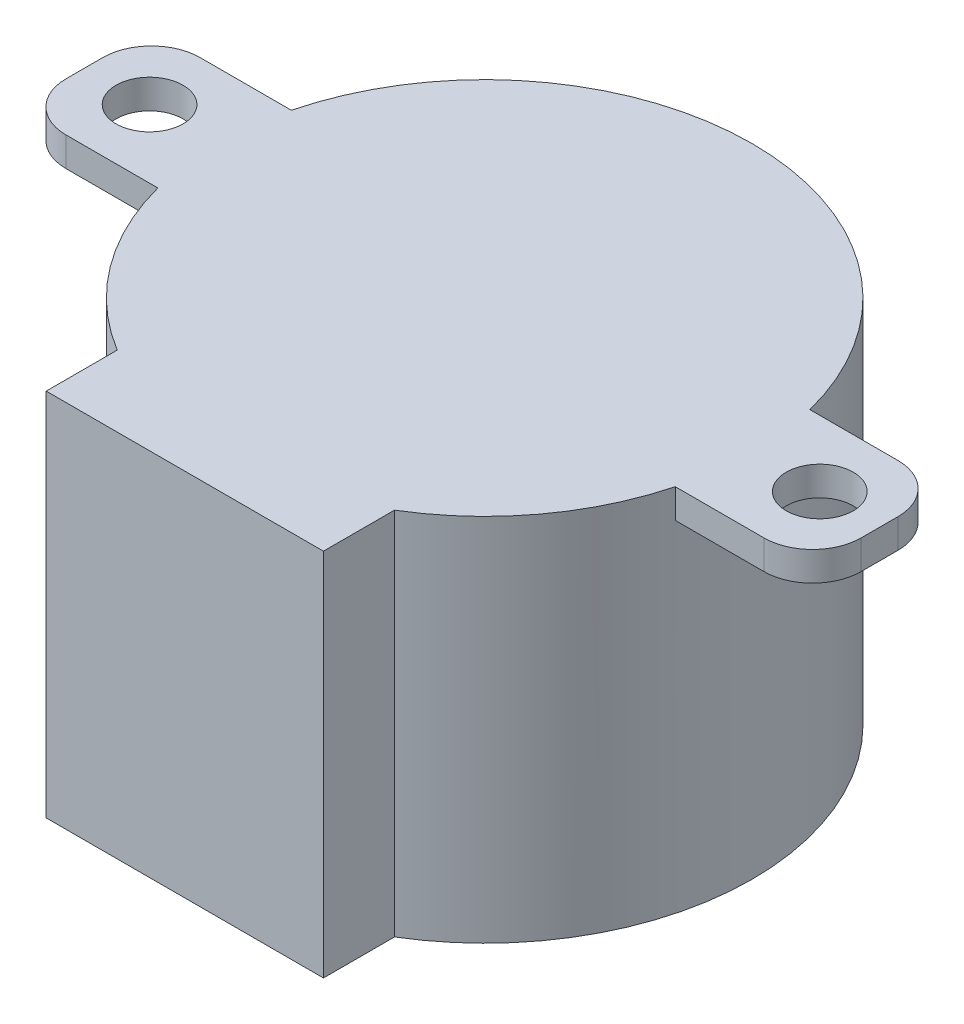
SolidWorks part; units mm, degrees
ref_plane "Front Plane" through (0, 0, 0) normal (0, 0, 1) x (1, 0, 0)
ref_plane "Top Plane" through (0, 0, 0) normal (0, 1, 0) x (1, 0, 0)
ref_plane "Right Plane" through (0, 0, 0) normal (1, 0, 0) x (0, 0, -1)
sketch "Sketch1" plane through (0, 0, 0) normal (0, 1, 0) x (1, 0, 0)
  line L0 (0, 0) -> (0, 11.5153) construction
  line L2 (-7.239, -11.9481) -> (-7.239, -15.6583)
  line L3 (-7.239, -15.6583) -> (7.239, -15.6583)
  line L4 (7.239, -11.9481) -> (7.239, -15.6583)
  line L5 (-18.3054, 3.444) -> (-13.5388, 3.444)
  line L6 (-20.8454, 0.904) -> (-20.8454, -1.016)
  line L7 (-18.3054, -3.556) -> (-13.5098, -3.556)
  line L8 (20.679, 0.904) -> (20.679, -1.016)
  line L9 (13.5388, 3.444) -> (18.139, 3.444)
  line L10 (13.5098, -3.556) -> (18.139, -3.556)
  arc A0 (7.239, -11.9481) -> (13.5098, -3.556) centre (0, 0) ccw
  circle A1 centre (17.5, 0) radius 1.75
  circle A2 centre (-17.5, 0) radius 1.75
  arc A3 (-18.3054, 3.444) -> (-20.8454, 0.904) centre (-18.3054, 0.904) ccw
  arc A4 (-20.8454, -1.016) -> (-18.3054, -3.556) centre (-18.3054, -1.016) ccw
  arc A5 (18.139, -3.556) -> (20.679, -1.016) centre (18.139, -1.016) ccw
  arc A6 (18.139, 3.444) -> (20.679, 0.904) centre (18.139, 0.904) cw
  arc A7 (-13.5098, -3.556) -> (-7.239, -11.9481) centre (0, 0) ccw
  arc A8 (13.5388, 3.444) -> (-13.5388, 3.444) centre (0, 0) ccw
  point P21 (20.679, -3.556)
  point P24 (20.679, 3.444)
  dimension "D1" = 27.94
  dimension "D4" = 3.5
  dimension "D8" = 2.54
  dimension "D2" = 14.478
  dimension "D3" = 7.239
  dimension "D5" = 7
  dimension "D6" = 3.556
  dimension "D7" = 17.5
extrude "Boss-Extrude1" add sketch "Sketch1" along normal blind 19.304
sketch "Sketch2" plane through (0, 19.304, 0) normal (0, 1, 0) x (1, 0, 0)
  line L0 (-13.5388, 3.444) -> (-18.3054, 3.444)
  line L2 (-18.3054, -3.556) -> (-13.5098, -3.556) construction
  line L3 (-18.3054, -3.556) -> (-13.5098, -3.556)
  line L4 (0, 0) -> (0, 19.2634) construction
  line L5 (18.3054, -3.556) -> (13.5098, -3.556)
  line L6 (20.8454, 0.904) -> (20.7779, -1.598)
  line L7 (13.5388, 3.444) -> (18.3054, 3.444)
  line L8 (-18.3054, 3.444) -> (-22.3791, 3.444)
  line L9 (-22.3791, 3.444) -> (-22.3791, -3.5987)
  line L10 (-22.3791, -3.5987) -> (-18.3054, -3.556)
  arc A0 (-13.5388, 3.444) -> (-13.5098, -3.556) centre (0, 0) ccw
  arc A4 (20.7779, -1.598) -> (18.3054, -3.556) centre (18.7224, -1.5425) cw
  arc A5 (18.3054, 3.444) -> (20.8454, 0.904) centre (18.3054, 0.904) cw
  arc A6 (13.5388, 3.444) -> (13.5098, -3.556) centre (0, 0) cw
extrude "Cut-Extrude1" cut sketch "Sketch2" along normal blind 17.78 from surface starting at face at (-0.0416, 0, 2.9112)
equation "\"D3@Sketch1\"=.57/2"
equation "\"D6@Sketch1\"=.28/2"
equation "\"D7@Sketch1\"=1.37795/2"
